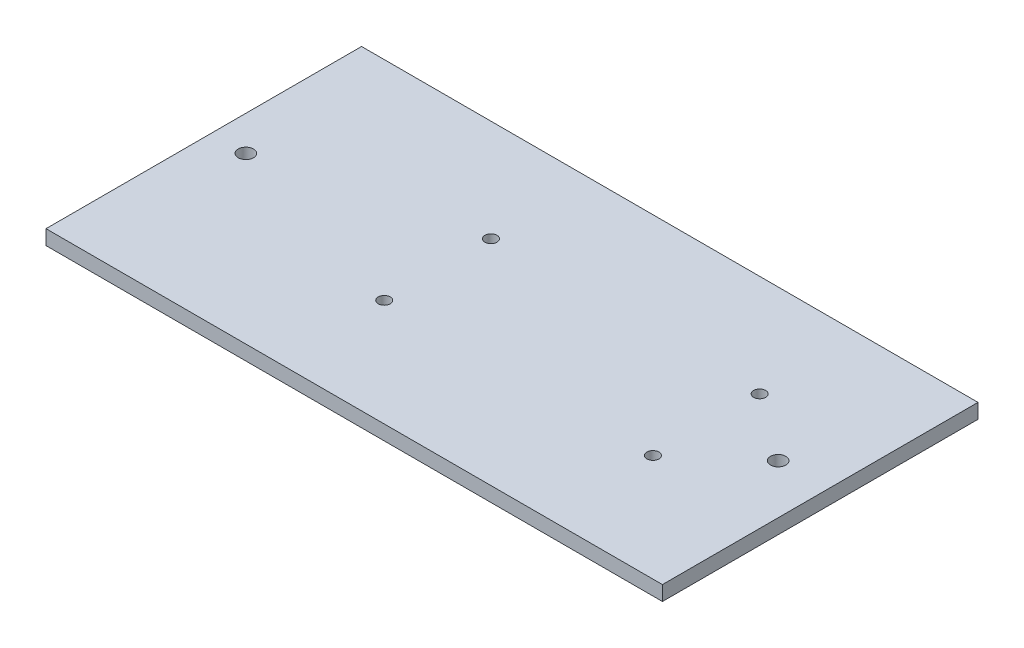
SolidWorks part; units mm, degrees
ref_plane "Front Plane" through (0, 0, 0) normal (0, 0, 1) x (1, 0, 0)
ref_plane "Top Plane" through (0, 0, 0) normal (0, 1, 0) x (1, 0, 0)
ref_plane "Right Plane" through (0, 0, 0) normal (1, 0, 0) x (0, 0, -1)
sketch "Sketch1" plane through (0, 0, 0) normal (0, 1, 0) x (1, 0, 0)
  line L0 (0, 34.0875) -> (0, -34.0875) construction
  line L1 (-66.5875, 34.0875) -> (66.5875, 34.0875)
  line L2 (-66.5875, 34.0875) -> (-66.5875, -34.0875)
  line L3 (-66.5875, -34.0875) -> (66.5875, -34.0875)
  line L4 (66.5875, 34.0875) -> (66.5875, -34.0875)
  line L5 (-66.5875, 34.0875) -> (66.5875, -34.0875) construction
  line L6 (-66.5875, -34.0875) -> (66.5875, 34.0875) construction
  line L7 (-59.0875, 26.5875) -> (55.9125, 26.5875) construction
  line L8 (-59.0875, 26.5875) -> (-59.0875, -23.4125) construction
  line L9 (-59.0875, -23.4125) -> (55.9125, -23.4125) construction
  line L10 (55.9125, 26.5875) -> (55.9125, -23.4125) construction
  line L11 (-66.5875, 0) -> (66.5875, 0) construction
  circle A1 centre (-59.0875, 1.5875) radius 1.65
  circle A2 centre (55.9125, 1.5875) radius 1.65
  point P0 (0, 0)
  point P6 (0, 0)
  dimension "D1" = 133.175
  dimension "D2" = 7.5
  dimension "D3" = 7.5
  dimension "D4" = 10.675
  dimension "D5" = 10.675
  dimension "D6" = 68.175
extrude "Boss-Extrude1" add sketch "Sketch1" along normal blind 3.175
sketch "Sketch2" plane through (0, 0, 0) normal (0, -1, 0) x (1, 0, 0)
  line L0 (66.5875, -34.0875) -> (-66.5875, -34.0875) construction
  line L1 (-16.6375, 10.9625) -> (41.4125, 10.9625) construction
  line L2 (-16.6375, 10.9625) -> (-16.6375, -12.0875) construction
  line L3 (-16.6375, -12.0875) -> (41.4125, -12.0875) construction
  line L4 (41.4125, 10.9625) -> (41.4125, -12.0875) construction
  line L5 (-16.6375, 10.9625) -> (41.4125, -12.0875) construction
  line L6 (-16.6375, -12.0875) -> (41.4125, 10.9625) construction
  line L8 (66.5875, 34.0875) -> (66.5875, -34.0875) construction
  circle A0 centre (-16.6375, 10.9625) radius 1.3
  circle A1 centre (-16.6375, -12.0875) radius 1.3
  circle A2 centre (41.4125, -12.0875) radius 1.3
  circle A3 centre (41.4125, 10.9625) radius 1.3
  point P0 (12.3875, -0.5625)
  dimension "D3" = 2.6
  dimension "D1" = 58.05
  dimension "D2" = 23.05
  dimension "D4" = 22
  dimension "D5" = 25.175
extrude "Cut-Extrude1" cut sketch "Sketch2" against normal up to surface (3.175 mm away) up to face at (-59.0875, 3.175, 0.0625)
